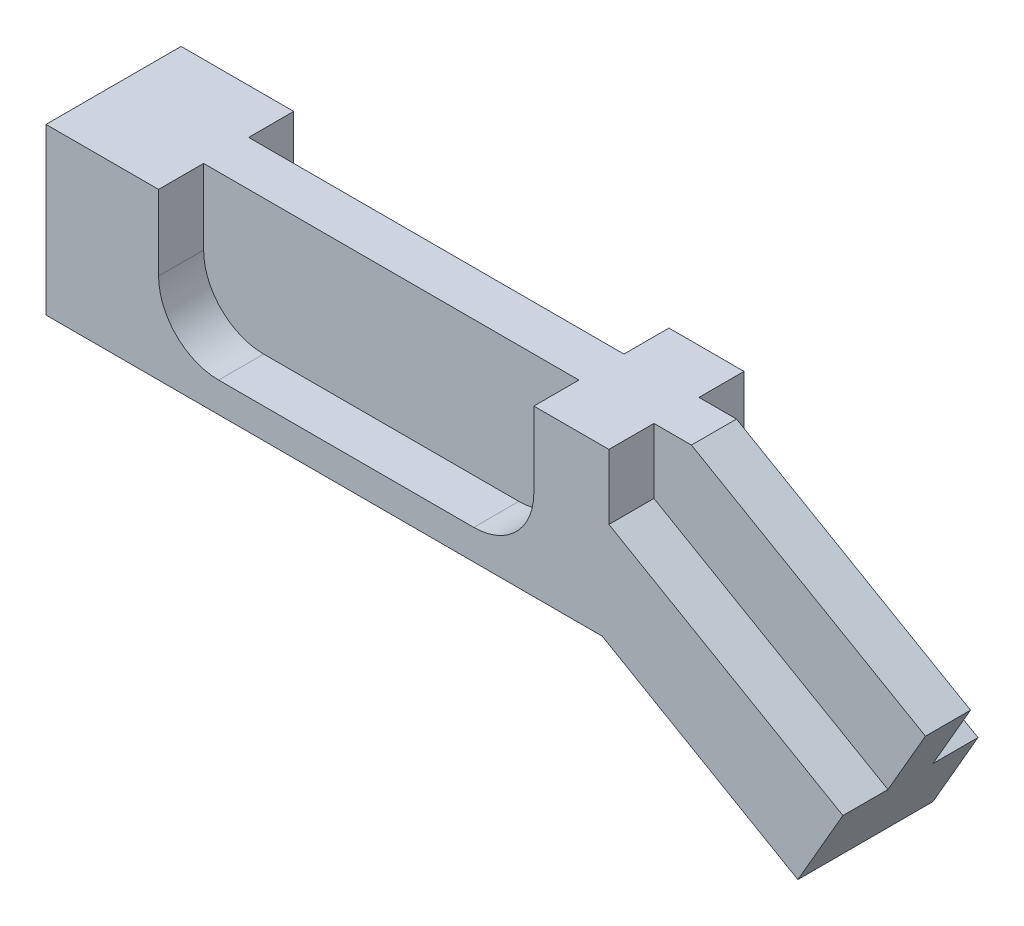
SolidWorks part; units mm, degrees
ref_plane "정면" through (0, 0, 0) normal (0, 0, 1) x (1, 0, 0)
ref_plane "윗면" through (0, 0, 0) normal (0, 1, 0) x (1, 0, 0)
ref_plane "우측면" through (0, 0, 0) normal (1, 0, 0) x (0, 0, -1)
sketch "스케치1" plane through (0, 0, 0) normal (0, 0, 1) x (1, 0, 0)
  line L0 (75, 0) -> (80, 0)
  line L1 (0, 0) -> (75, 0)
  line L2 (0, 0) -> (0, -22)
  line L3 (0, -22) -> (74.1051, -22)
  line L4 (75, 0) -> (75, -8.6603)
  line L5 (15, 0) -> (65, 0)
  line L6 (15, 0) -> (15, -10)
  line L7 (23, -18) -> (57, -18)
  line L8 (65, 0) -> (65, -10)
  line L9 (80, 0) -> (111.1769, -18)
  line L10 (111.1769, -18) -> (100.1769, -37.0526)
  line L11 (100.1769, -37.0526) -> (74.1051, -22)
  line L12 (106.1769, -26.6603) -> (75, -8.6603)
  arc A0 (15, -10) -> (23, -18) centre (23, -10) ccw
  arc A1 (57, -18) -> (65, -10) centre (57, -10) ccw
  point P11 (15, -18)
  point P14 (65, -18)
  dimension "D6" = 8
  dimension "D7" = 8
  dimension "D1" = 75
  dimension "D2" = 22
  dimension "D3" = 50
  dimension "D4" = 18
  dimension "D5" = 15
  dimension "D8" = 5
  dimension "D9" = 36
  dimension "D10" = 30
  dimension "D11" = 22
  dimension "D12" = 12
extrude "보스-돌출1" add sketch "스케치1" along normal mid plane 18 contours A1 L7 A0 L6 L1 L2 L3 L11 L10 L12 L4 L8 region at (73.8754, -4.3301, 0)
extrude "보스-돌출2" add sketch "스케치1<3>" along normal mid plane 6 contours L7 A1 L8 L1 L6 A0 | L12 L10 L9 L0 L4 region at (92.1569, -12.7377, 0) region at (40, -8.7729, 0)
sketch "스케치1<3>" plane through (0, 0, 0) normal (0, 0, 1) x (1, 0, 0) same geometry as "스케치1"
